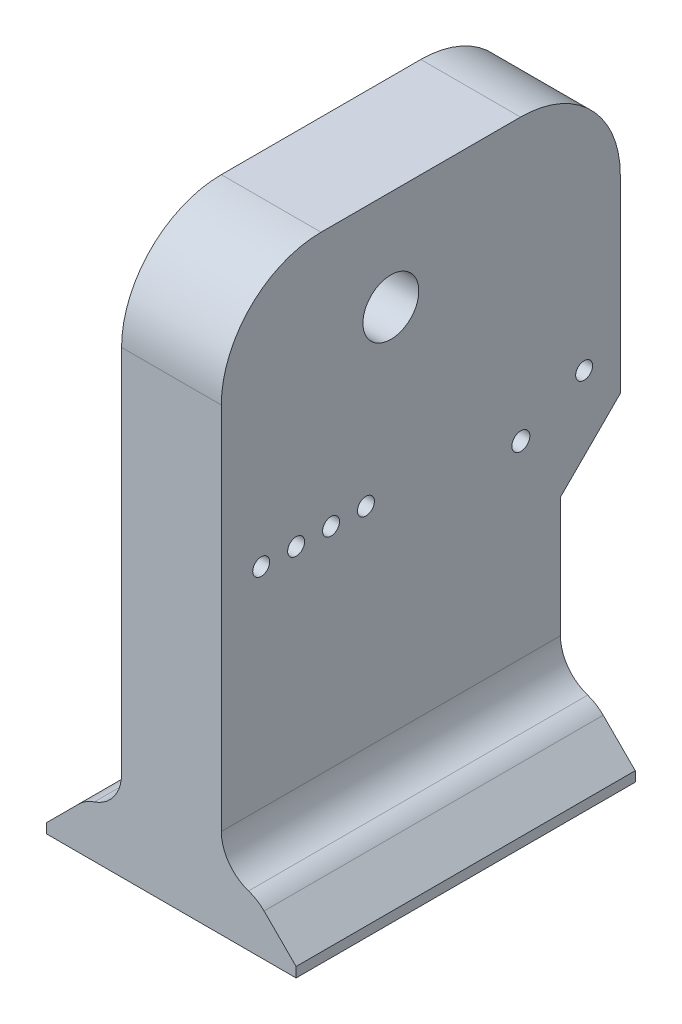
SolidWorks part; units mm, degrees
ref_plane "Front Plane" through (0, 0, 0) normal (0, 0, 1) x (1, 0, 0)
ref_plane "Top Plane" through (0, 0, 0) normal (0, 1, 0) x (1, 0, 0)
ref_plane "Right Plane" through (0, 0, 0) normal (1, 0, 0) x (0, 0, -1)
sketch "Sketch1" plane through (0, 0, 0) normal (0, 1, 0) x (1, 0, 0)
  line L0 (0, 17) -> (0, -17) construction
  line L1 (-12.5, -17) -> (12.5, -17)
  line L2 (-12.5, -17) -> (-12.5, 17)
  line L3 (-12.5, 17) -> (12.5, 17)
  line L4 (12.5, -17) -> (12.5, 17)
  line L5 (-12.5, -17) -> (12.5, 17) construction
  line L6 (-12.5, 17) -> (12.5, -17) construction
  point P2 (0, 0)
  dimension "D1" = 34
  dimension "D2" = 25
extrude "Boss-Extrude1" add sketch "Sketch1" along normal blind 5
sketch "Sketch2" plane through (0, 5, 0) normal (0, 1, 0) x (1, 0, 0)
  line L0 (12.5, 17) -> (-12.5, 17) construction
  line L1 (-5, -17) -> (5, -17)
  line L2 (-5, -17) -> (-5, 17)
  line L3 (-5, 17) -> (5, 17)
  line L4 (5, -17) -> (5, 17)
  line L5 (-5, -17) -> (5, 17) construction
  line L6 (-5, 17) -> (5, -17) construction
  point P0 (0, 0)
  dimension "D1" = 10
extrude "Boss-Extrude2" add sketch "Sketch2" along normal blind 51
sketch "Sketch3" plane through (-5, 0, 0) normal (-1, 0, 0) x (0, 0, 1)
  line L0 (0, 56) -> (0, 46) construction
  line L1 (-17, 56) -> (17, 56) construction
  circle A0 centre (0, 46) radius 2.8
  dimension "D1" = 10
extrude "Cut-Extrude1" cut sketch "Sketch3" against normal blind 41
chamfer "Chamfer1" distance 4 angle 45 2 edges at (12.5, 5, 0) (-12.5, 5, 0)
fillet "Fillet1" radius 4 2 edges at (5, 5, 0) (-5, 5, 0)
fillet "Fillet2" radius 4 2 edges at (8.5, 5, 0) (-8.5, 5, 0)
sketch "Sketch4" plane through (-5, 0, 0) normal (-1, 0, 0) x (0, 0, 1)
  line L0 (17, 8.9686) -> (17, 29.9686) construction
  line L1 (0, 56) -> (50.815, 56) construction
  line L2 (0, 56) -> (0, 36) construction
  line L3 (0, 36) -> (50.815, 36) construction
  line L4 (50.815, 56) -> (50.815, 36) construction
  line L5 (17, 56) -> (17, 8.9686) construction
  line L6 (17, 29.9686) -> (13, 29.9686) construction
  line L7 (13, 29.9686) -> (6, 29.9686) construction
  line L8 (9.5, 29.9686) -> (2.5, 29.9686) construction
  line L9 (-10, 46) -> (10, 46) construction
  line L10 (-10, 46) -> (-10, 65.9551) construction
  line L11 (-10, 65.9551) -> (10, 65.9551) construction
  line L12 (10, 46) -> (10, 65.9551) construction
  circle A0 centre (0, 46) radius 10 construction
  circle A1 centre (6, 29.9686) radius 0.85
  circle A2 centre (13, 29.9686) radius 0.85
  circle A3 centre (2.5, 29.9686) radius 0.85
  circle A4 centre (9.5, 29.9686) radius 0.85
  dimension "D1" = 21
  dimension "D2" = 4
  dimension "D3" = 7
extrude "Cut-Extrude2" cut sketch "Sketch4" against normal blind 41
sketch "Sketch5" plane through (0, 0, -17) normal (0, 0, -1) x (-1, 0, 0)
  line L0 (5, 56) -> (5, 8.9686) construction
  line L1 (-5, 56) -> (5, 56)
  line L2 (-5, 56) -> (-5, 36)
  line L3 (-5, 36) -> (5, 36)
  line L4 (5, 56) -> (5, 36)
extrude "Boss-Extrude3" add sketch "Sketch5" along normal blind 6
sketch "Sketch6" plane through (-5, 0, 0) normal (-1, 0, 0) x (0, 0, 1)
  line L0 (-8.888, 50.583) -> (0.6207, 69.0232)
  line L1 (-8.888, 50.583) -> (-15.1095, 53.7912) construction
  circle A0 centre (0, 46) radius 10
  dimension "D1" = 7
chamfer "Chamfer3" distance 15 angle 45 1 edges at (0, 36, -17)
fillet "Fillet4" radius 10 2 edges at (0, 56, 17) (0, 56, -23)
sketch "Sketch7" plane through (5, 0, 0) normal (1, 0, 0) x (0, 0, -1)
  line L4 (23, 27) -> (23, 32.5) construction
  line L5 (23, 32.5) -> (19.3748, 30.8095) construction
  line L6 (19.3748, 30.8095) -> (13.0306, 27.8512) construction
  circle A0 centre (13.0306, 27.8512) radius 0.9
  circle A1 centre (19.3748, 30.8095) radius 0.85
  point P12 (19.9907, 38.9027)
  dimension "D4" = 5.5
  dimension "D1" = 65
  dimension "D2" = 4
  dimension "D3" = 7
extrude "Cut-Extrude3" cut sketch "Sketch7" against normal blind 13
